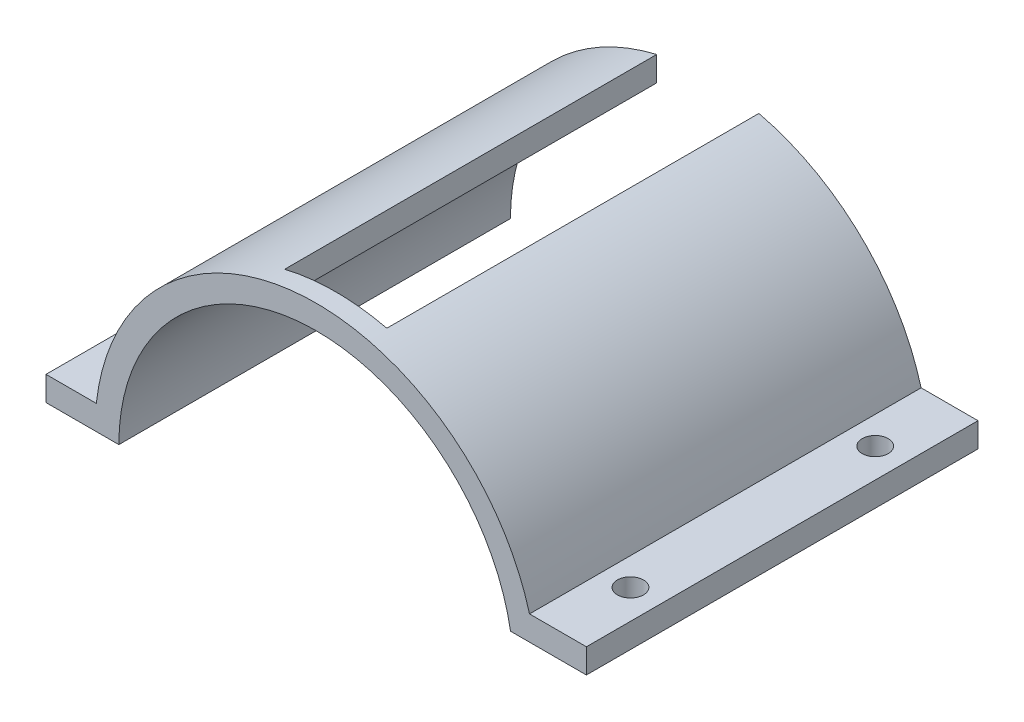
SolidWorks part; units mm, degrees
note: The reader was unsure of these and kept them because the rebuilt part matched: shared geometry of "Sketch1<4>".
ref_plane "Front Plane" through (0, 0, 0) normal (0, 0, 1) x (1, 0, 0)
ref_plane "Top Plane" through (0, 0, 0) normal (0, 1, 0) x (1, 0, 0)
ref_plane "Right Plane" through (0, 0, 0) normal (1, 0, 0) x (0, 0, -1)
sketch "Sketch1" plane through (0, 0, 0) normal (0, 0, 1) x (1, 0, 0)
  line L0 (0, 0) -> (-57.404, 0) construction
  line L1 (0, 0) -> (57.404, 0) construction
  line L4 (-56.7112, -8.8915) -> (-56.7112, -57.404)
  line L5 (-56.7112, -57.404) -> (57.404, -57.404)
  line L6 (57.404, -57.404) -> (57.404, 0)
  line L7 (57.2303, 4.4627) -> (70.104, 4.4627)
  line L8 (70.104, 4.4627) -> (70.104, -57.404)
  line L9 (70.104, -57.404) -> (57.404, -57.404)
  line L10 (-56.7112, -8.8915) -> (-70.104, -8.8915)
  line L11 (-70.104, -8.8915) -> (-70.104, -57.404)
  line L12 (-70.104, -57.404) -> (-56.7112, -57.404)
  line L13 (-56.7112, -8.8915) -> (-56.7112, -57.404)
  line L14 (0, 0) -> (-13.2526, 49.4593)
  line L15 (-13.2526, 49.4593) -> (-13.2526, 55.8533)
  line L16 (0, 0) -> (-57.404, 0)
  line L17 (0, 0) -> (-57.404, 0)
  line L18 (-57.404, 0) -> (-70.104, 0)
  line L19 (-70.104, 0) -> (-70.104, 6.35)
  line L20 (0, 0) -> (-50.4261, -8.8915)
  line L21 (-50.4261, -8.8915) -> (-56.7112, -8.8915)
  line L22 (0, 0) -> (51.0092, 4.4627)
  line L23 (51.0092, 4.4627) -> (57.2303, 4.4627)
  line L24 (-70.104, 6.35) -> (-57.0517, 6.35)
  line L25 (0, 0) -> (13.2526, 49.4593)
  line L26 (13.2526, 49.4593) -> (13.2526, 55.8533)
  line L27 (0, 0) -> (50.4261, 8.8915)
  line L28 (70.104, 15.2415) -> (55.3436, 15.2415)
  line L29 (50.4261, 8.8915) -> (56.7112, 8.8915)
  line L30 (56.7112, 8.8915) -> (70.104, 8.8915)
  line L31 (70.104, 8.8915) -> (70.104, 15.2415)
  line L32 (0, 0) -> (0, 57.404) construction
  circle A0 centre (0, 0) radius 51.204
  circle A1 centre (0, 0) radius 57.404
  dimension "D1" = 102.408
  dimension "D3" = 5
  dimension "D4" = 175
  dimension "D5" = 12.7
  dimension "D6" = 12.7
  dimension "D8" = 6.35
  dimension "D10" = 5
  dimension "D11" = 6.35
  dimension "D7" = 15
  dimension "D9" = 15
  dimension "D2" = 6.2
extrude "Boss-Extrude1" add sketch "Sketch1" along normal mid plane 101.6
extrude "Boss-Extrude2" add sketch "Sketch1<4>" against normal blind 5.08 from surface at 50.8 contours L26 A1 L15 A0 starting at face at (-48.5339, 21.8984, 50.8)
sketch "Sketch1<4>" plane through (0, 0, 0) normal (0, 0, 1) x (1, 0, 0) same geometry as "Sketch1"
sketch "Sketch2" plane through (0, 6.35, 0) normal (0, 1, 0) x (1, 0, 0)
  line L0 (-62.484, 50.8) -> (-62.484, -50.8) construction
  line L1 (-70.104, 50.8) -> (-57.0517, 50.8) construction
  line L2 (-70.104, -50.8) -> (-57.0517, -50.8) construction
  line L3 (-70.104, -50.8) -> (-70.104, 50.8) construction
  point P6 (-62.484, 0)
  point P7 (-62.484, 31.75)
  point P8 (-62.484, -31.75)
  dimension "D1" = 7.62
  dimension "D2" = 31.75
  dimension "D3" = 31.75
hole_wizard "1/4 Clearance Hole1" positions "Sketch2" profile "Sketch3" hole size "1/4" standard "ANSI Inch"
sketch "Sketch3" plane through (-62.484, 6.35, 31.75) normal (1, 0, 0) x (0, 0, 1)
  line L0 (0, 0) -> (0, 6.35)
  line L1 (0, 6.35) -> (3.3782, 6.35)
  line L2 (3.3782, 6.35) -> (3.3782, 0)
  line L5 (3.3782, 0) -> (0, 0)
  line L11 (0, -6.35) -> (0, 107.95) construction
  dimension "Thru Hole Dia." = 6.7564
  dimension "Thru Hole Depth" = 6.35
sketch "Sketch4" plane through (0, 15.2415, 0) normal (0, 1, 0) x (1, 0, 0)
  line L0 (62.484, 50.8) -> (62.484, -50.8) construction
  line L1 (70.104, 50.8) -> (55.3436, 50.8) construction
  line L2 (70.104, -50.8) -> (55.3436, -50.8) construction
  line L3 (70.104, -50.8) -> (70.104, 50.8) construction
  point P6 (62.484, 0)
  point P7 (62.484, 31.75)
  point P8 (62.484, -31.75)
  dimension "D1" = 7.62
  dimension "D2" = 31.75
  dimension "D3" = 31.75
hole_wizard "1/4 Clearance Hole2" positions "Sketch4" profile "Sketch5" hole size "1/4" standard "ANSI Inch"
sketch "Sketch5" plane through (62.484, 15.2415, 31.75) normal (1, 0, 0) x (0, 0, 1)
  line L0 (0, 0) -> (0, 15.2415)
  line L1 (0, 15.2415) -> (3.3782, 15.2415)
  line L2 (3.3782, 15.2415) -> (3.3782, 0)
  line L5 (3.3782, 0) -> (0, 0)
  line L11 (0, -6.35) -> (0, 107.95) construction
  dimension "Thru Hole Dia." = 6.7564
  dimension "Thru Hole Depth" = 15.2415
equation "\"tolerance\" = 0.3mm"
equation "\"D1@Sketch1\"=4.02 + \"tolerance\""
equation "\"D2@Sketch1\"=0.25 - \"tolerance\"/2"
